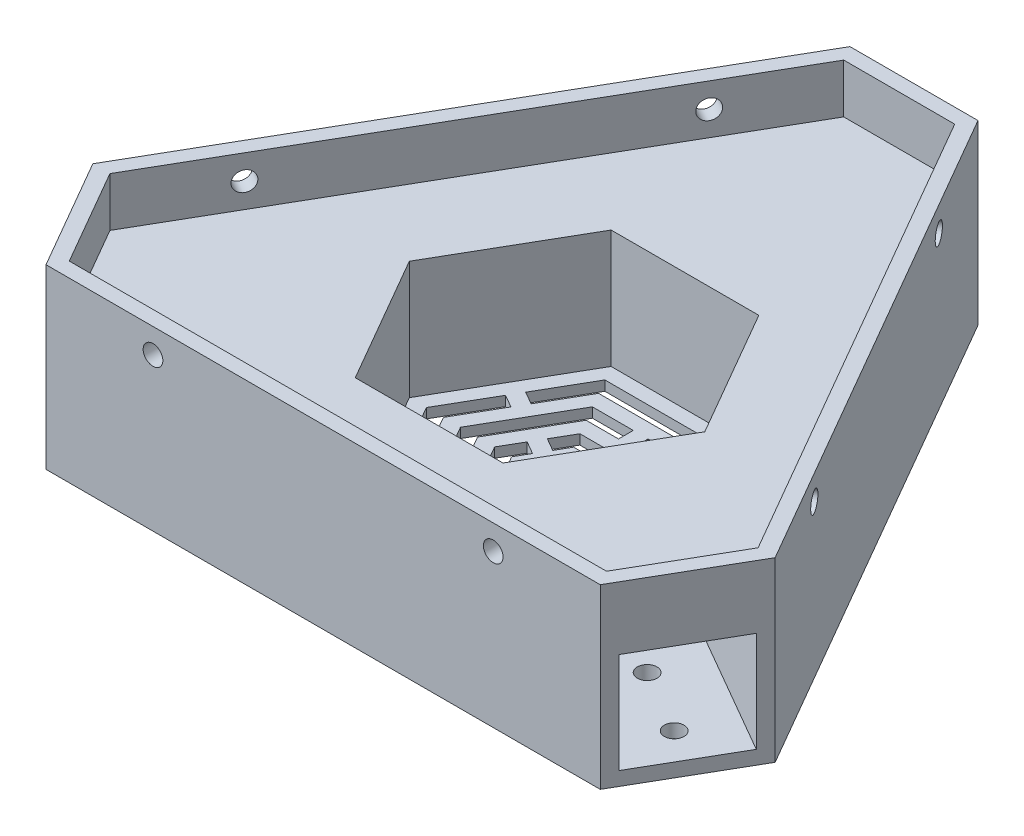
SolidWorks part; units mm, degrees
ref_plane "Front Plane" through (0, 0, 0) normal (0, 0, 1) x (1, 0, 0)
ref_plane "Top Plane" through (0, 0, 0) normal (0, 1, 0) x (1, 0, 0)
ref_plane "Right Plane" through (0, 0, 0) normal (1, 0, 0) x (0, 0, -1)
sketch "Sketch1" plane through (0, 0, 0) normal (0, 1, 0) x (1, 0, 0)
  line L0 (-11.2679, 69.4944) -> (11.2679, 69.4944)
  line L1 (15, 25.9808) -> (-15, 25.9808)
  line L2 (-15, 25.9808) -> (-30, 0)
  line L3 (-30, 0) -> (-15, -25.9808)
  line L4 (-15, -25.9808) -> (15, -25.9808)
  line L5 (15, -25.9808) -> (30, 0)
  line L6 (30, 0) -> (15, 25.9808)
  line L7 (-11.2679, 69.4944) -> (-38.5429, 22.2528)
  line L8 (11.2679, 69.4944) -> (38.5429, 22.2528)
  line L9 (41.141, 23.7528) -> (13, 72.4944)
  line L10 (13, 72.4944) -> (-13, 72.4944)
  line L11 (-13, 72.4944) -> (-41.141, 23.7528)
  line L12 (0, 0) -> (0, 113.4171) construction
  line L13 (0, 0) -> (-77.6761, 44.8463) construction
  line L14 (0, 0) -> (87.0373, 50.251) construction
  line L15 (69.282, -24.9889) -> (41.141, 23.7528)
  line L16 (65.8179, -24.9889) -> (38.5429, 22.2528)
  line L17 (56.282, -47.5056) -> (69.282, -24.9889)
  line L18 (65.8179, -24.9889) -> (54.55, -44.5056)
  line L19 (0, -47.5056) -> (56.282, -47.5056)
  line L20 (54.55, -44.5056) -> (0, -44.5056)
  line L21 (-56.282, -47.5056) -> (0, -47.5056)
  line L22 (-54.55, -44.5056) -> (0, -44.5056)
  line L23 (-69.282, -24.9889) -> (-56.282, -47.5056)
  line L24 (-54.55, -44.5056) -> (-65.8179, -24.9889)
  line L25 (-41.141, 23.7528) -> (-69.282, -24.9889)
  line L26 (-65.8179, -24.9889) -> (-38.5429, 22.2528)
  circle A0 centre (0, 0) radius 25.9808 construction
  point P15 (0, 69.4944)
  point P19 (0, 72.4944)
  point P20 (73.9049, -55.6801)
  point P41 (0, 0)
  dimension "D1" = 30
  dimension "D2" = 3
  dimension "D3" = 3
  dimension "D5" = 26
  dimension "D6" = 120
  dimension "D4" = 3
extrude "Boss-Extrude1" add sketch "Sketch1" along normal blind 2 contours L5 L6 L1 L2 L3 L4 region at (0, 0, 0)
extrude "Boss-Extrude2" add sketch "Sketch1<3>" along normal blind 26 contours L11 L25 L23 L21 L19 L17 L15 L9 L10 L24 L26 L7 L0 L8 L16 L18 L20 L22 | L26 L24 L22 L20 L18 L16 L8 L0 L7 L6 L5 L4 L3 L2 L1 region at (0, 0, -67.7531) region at (53.6241, 0, 1.5346)
sketch "Sketch1<3>" plane through (0, 0, 0) normal (0, 1, 0) x (1, 0, 0) same geometry as "Sketch1"
sketch "Sketch2" plane through (62.782, 0, 36.2472) normal (0.866, 0, 0.5) x (0.5, 0, -0.866)
  line L0 (-13, 26) -> (13, 0) construction
  line L1 (13, 26) -> (-13, 0) construction
  line L3 (-10.2, 2.8) -> (10.2, 2.8)
  line L4 (-10.2, 2.8) -> (-10.2, 23.2)
  line L5 (-10.2, 23.2) -> (10.2, 23.2)
  line L6 (10.2, 2.8) -> (10.2, 23.2)
  line L7 (-10.2, 2.8) -> (10.2, 23.2) construction
  line L8 (-10.2, 23.2) -> (10.2, 2.8) construction
  point P8 (0, 13)
  dimension "D1" = 20.4
extrude "Cut-Extrude1" cut sketch "Sketch2" against normal blind 30
ref_axis "Axis1" through (0, 27.3, 0) along (0, -1, 0)
pattern_circular "CirPattern1" count 3 over 360 about axis through (0, 27.3, 0) along (0, -1, 0) of "Cut-Extrude1"
sketch "Sketch3" plane through (0, 26, 0) normal (0, 1, 0) x (1, 0, 0)
  line L0 (-15, -25.9808) -> (15, -25.9808)
  line L1 (15, -25.9808) -> (30, 0)
  line L2 (30, 0) -> (15, 25.9808)
  line L3 (15, 25.9808) -> (-15, 25.9808)
  line L4 (-15, 25.9808) -> (-30, 0)
  line L5 (-30, 0) -> (-15, -25.9808)
  line L6 (0, -25.9808) -> (0, 25.9808) construction
  line L7 (1.5, 25.9808) -> (1.5, -25.9808) construction
  line L8 (-1.5, 25.9808) -> (-1.5, -25.9808) construction
  line L9 (23.25, -11.6913) -> (-21.75, 14.2894) construction
  line L10 (-22.5, 12.9904) -> (22.5, -12.9904) construction
  line L11 (21.75, -14.2894) -> (-23.25, 11.6913) construction
  line L12 (-21.75, -14.2894) -> (23.25, 11.6913) construction
  line L13 (22.5, 12.9904) -> (-22.5, -12.9904) construction
  line L14 (-23.25, -11.6913) -> (21.75, 14.2894) construction
  line L15 (30, 0) -> (15, 25.9808) construction
  line L16 (0, 22.9808) -> (13.2679, 22.9808)
  line L17 (13.2679, 22.9808) -> (19.1519, 12.7894)
  line L18 (19.1519, 12.7894) -> (16.5538, 11.2894)
  line L19 (16.5538, 11.2894) -> (11.5359, 19.9808)
  line L20 (11.5359, 19.9808) -> (0, 19.9808)
  line L21 (19.6077, 0) -> (9.8038, 16.9808)
  line L22 (9.8038, 16.9808) -> (1.5, 16.9808)
  line L23 (1.5, 16.9808) -> (1.5, 13.9808)
  line L24 (1.5, 13.9808) -> (8.0718, 13.9808)
  line L25 (8.0718, 13.9808) -> (16.1436, 0)
  line L26 (6.1615, 5.2894) -> (8.7596, 6.7894)
  line L27 (8.7596, 6.7894) -> (6.3397, 10.9808)
  line L28 (6.3397, 10.9808) -> (0, 10.9808)
  line L29 (8.7596, 6.7894) -> (10.2596, 4.1913)
  line L30 (6.1615, 5.2894) -> (7.6615, 2.6913)
  line L31 (6.1615, 5.2894) -> (4.6077, 7.9808)
  line L32 (4.6077, 7.9808) -> (1.5, 7.9808)
  line L33 (1.5, 7.9808) -> (0, 7.9808)
  line L34 (1.5, 7.9808) -> (1.5, 4.9808)
  line L35 (1.5, 4.9808) -> (2.8756, 4.9808)
  line L36 (2.8756, 4.9808) -> (5.7513, 0)
  line L37 (7.6615, -2.6913) -> (5.0635, -1.1913)
  line L38 (7.6615, 2.6913) -> (10.2596, 4.1913)
  line L39 (15.4558, -7.1913) -> (12.8577, -5.6913)
  line L40 (20.6519, 10.1913) -> (18.0538, 8.6913)
  line L41 (5.0635, -1.1913) -> (5.7513, 0)
  line L42 (7.6615, 2.6913) -> (9.2154, 0)
  line L43 (7.6615, -2.6913) -> (6.9115, -3.9904)
  line L44 (9.2154, 0) -> (7.6615, -2.6913)
  line L45 (10.2596, 4.1913) -> (12.6795, 0)
  line L46 (12.6795, 0) -> (9.5096, -5.4904)
  line L47 (12.8577, -5.6913) -> (16.1436, 0)
  line L48 (19.6077, 0) -> (15.4558, -7.1913)
  line L49 (18.0538, 8.6913) -> (23.0718, 0)
  line L50 (23.0718, 0) -> (17.3038, -9.9904)
  line L51 (26.5359, 0) -> (20.6519, 10.1913)
  line L52 (19.9019, -11.4904) -> (26.5359, 0)
  line L53 (19.9019, -11.4904) -> (13.2679, -22.9808)
  line L54 (13.2679, -22.9808) -> (1.5, -22.9808)
  line L55 (1.5, -22.9808) -> (1.5, -19.9808)
  line L56 (1.5, -19.9808) -> (11.5359, -19.9808)
  line L57 (11.5359, -19.9808) -> (17.3038, -9.9904)
  line L58 (-9.8038, -16.9808) -> (9.8038, -16.9808)
  line L59 (9.8038, -16.9808) -> (13.9558, -9.7894)
  line L60 (13.9558, -9.7894) -> (11.3577, -8.2894)
  line L61 (11.3577, -8.2894) -> (8.0718, -13.9808)
  line L62 (8.0718, -13.9808) -> (-8.0718, -13.9808)
  line L63 (1.5, -7.9808) -> (1.5, -10.9808)
  line L64 (1.5, -10.9808) -> (6.3397, -10.9808)
  line L65 (6.3397, -10.9808) -> (9.5096, -5.4904)
  line L66 (1.5, -10.9808) -> (-1.5, -10.9808)
  line L67 (1.5, -7.9808) -> (-1.5, -7.9808)
  line L68 (1.5, -7.9808) -> (4.6077, -7.9808)
  line L69 (4.6077, -7.9808) -> (6.1615, -5.2894)
  line L70 (6.1615, -5.2894) -> (6.9115, -3.9904)
  line L71 (6.1615, -5.2894) -> (3.5635, -3.7894)
  line L72 (3.5635, -3.7894) -> (2.8756, -4.9808)
  line L73 (2.8756, -4.9808) -> (-2.8756, -4.9808)
  line L74 (-6.1615, -5.2894) -> (-3.5635, -3.7894)
  line L75 (-1.5, -7.9808) -> (-1.5, -10.9808)
  line L76 (-13.9558, -9.7894) -> (-11.3577, -8.2894)
  line L77 (-1.5, -22.9808) -> (-1.5, -19.9808)
  line L78 (-3.5635, -3.7894) -> (-2.8756, -4.9808)
  line L79 (-1.5, -7.9808) -> (-4.6077, -7.9808)
  line L80 (-6.1615, -5.2894) -> (-6.9115, -3.9904)
  line L81 (-4.6077, -7.9808) -> (-6.1615, -5.2894)
  line L82 (-1.5, -10.9808) -> (-6.3397, -10.9808)
  line L83 (-6.3397, -10.9808) -> (-9.5096, -5.4904)
  line L84 (-11.3577, -8.2894) -> (-8.0718, -13.9808)
  line L85 (-9.8038, -16.9808) -> (-13.9558, -9.7894)
  line L86 (-1.5, -19.9808) -> (-11.5359, -19.9808)
  line L87 (-11.5359, -19.9808) -> (-17.3038, -9.9904)
  line L88 (-13.2679, -22.9808) -> (-1.5, -22.9808)
  line L89 (-19.9019, -11.4904) -> (-13.2679, -22.9808)
  line L90 (-19.9019, -11.4904) -> (-26.5359, 0)
  line L91 (-26.5359, 0) -> (-20.6519, 10.1913)
  line L92 (-20.6519, 10.1913) -> (-18.0538, 8.6913)
  line L93 (-18.0538, 8.6913) -> (-23.0718, 0)
  line L94 (-23.0718, 0) -> (-17.3038, -9.9904)
  line L95 (-9.8038, 16.9808) -> (-19.6077, 0)
  line L96 (-19.6077, 0) -> (-15.4558, -7.1913)
  line L97 (-15.4558, -7.1913) -> (-12.8577, -5.6913)
  line L98 (-12.8577, -5.6913) -> (-16.1436, 0)
  line L99 (-16.1436, 0) -> (-8.0718, 13.9808)
  line L100 (-7.6615, 2.6913) -> (-10.2596, 4.1913)
  line L101 (-10.2596, 4.1913) -> (-12.6795, 0)
  line L102 (-12.6795, 0) -> (-9.5096, -5.4904)
  line L103 (-10.2596, 4.1913) -> (-8.7596, 6.7894)
  line L104 (-7.6615, 2.6913) -> (-6.1615, 5.2894)
  line L105 (-7.6615, 2.6913) -> (-9.2154, 0)
  line L106 (-9.2154, 0) -> (-7.6615, -2.6913)
  line L107 (-7.6615, -2.6913) -> (-6.9115, -3.9904)
  line L108 (-7.6615, -2.6913) -> (-5.0635, -1.1913)
  line L109 (-5.0635, -1.1913) -> (-5.7513, 0)
  line L110 (-5.7513, 0) -> (-2.8756, 4.9808)
  line L111 (-1.5, 7.9808) -> (-1.5, 4.9808)
  line L112 (-6.1615, 5.2894) -> (-8.7596, 6.7894)
  line L113 (-1.5, 16.9808) -> (-1.5, 13.9808)
  line L114 (-19.1519, 12.7894) -> (-16.5538, 11.2894)
  line L115 (-1.5, 4.9808) -> (-2.8756, 4.9808)
  line L116 (-6.1615, 5.2894) -> (-4.6077, 7.9808)
  line L117 (-1.5, 7.9808) -> (0, 7.9808)
  line L118 (-4.6077, 7.9808) -> (-1.5, 7.9808)
  line L119 (-8.7596, 6.7894) -> (-6.3397, 10.9808)
  line L120 (-6.3397, 10.9808) -> (0, 10.9808)
  line L121 (-1.5, 13.9808) -> (-8.0718, 13.9808)
  line L122 (-9.8038, 16.9808) -> (-1.5, 16.9808)
  line L123 (-16.5538, 11.2894) -> (-11.5359, 19.9808)
  line L124 (-11.5359, 19.9808) -> (0, 19.9808)
  line L125 (-13.2679, 22.9808) -> (-19.1519, 12.7894)
  line L126 (0, 22.9808) -> (-13.2679, 22.9808)
  line L127 (-1.5, 4.9808) -> (1.5, 4.9808)
  line L128 (5.0635, -1.1913) -> (3.5635, -3.7894)
  line L129 (-5.0635, -1.1913) -> (-3.5635, -3.7894)
  line L130 (15, 25.9808) -> (0, 0) construction
  point P34 (0, 0)
  point P58 (6.9115, 3.9904)
  point P66 (4.3135, 2.4904)
  point P68 (9.5096, 5.4904)
  point P71 (12.1077, 6.9904)
  point P72 (14.7058, 8.4904)
  point P76 (13.2679, 22.9808)
  point P78 (12.8577, 20.2978)
  point P79 (13.2679, 16.9808)
  point P80 (8.1205, 14.065)
  point P86 (6.4287, 9.0261)
  point P96 (0, 0)
  point P101 (3.2877, 5.6945)
  point P104 (0, -7.9808)
  point P112 (0, -4.9808)
  point P114 (0, -10.9808)
  point P117 (0, -13.9808)
  point P118 (0, -16.9808)
  point P123 (4.9027, 9.0261)
  point P129 (0, 0)
  point P139 (0, 9.0261)
  point P147 (-6.9115, 3.9904)
  point P155 (-4.3135, 2.4904)
  point P156 (5.2112, 9.0261)
  point P157 (-9.5096, 5.4904)
  point P158 (4.9027, 9.0261)
  point P160 (-12.1077, 6.9904)
  point P161 (-14.7058, 8.4904)
  point P162 (-4.9027, 9.0261)
  point P164 (1.5, 7.9808)
  point P165 (0, 0)
  point P166 (3.2684, 5.6611)
  point P167 (0, 0)
  point P168 (0, 0)
  point P169 (0, 0)
  point P170 (6.1615, 10.4199)
  point P171 (6.9115, 11.9028)
  point P172 (3.6742, 6.3639)
  point P173 (-1.5, 6.3639)
  point P174 (3.6742, -6.3639)
  point P175 (3.6742, 6.3639)
  point P176 (0, 0)
  point P177 (1.5, 6.103)
  point P178 (2.8756, 4.9808)
  dimension "D1" = 3
  dimension "D4" = 3
  dimension "D5" = 6
  dimension "D6" = 9
  dimension "D7" = 12
  dimension "D8" = 15
  dimension "D9" = 18
  dimension "D10" = 3
  dimension "D2" = 3
  dimension "D3" = 3
extrude "Cut-Extrude2" cut sketch "Sketch3" against normal through all contours L109 L129 L78 L73 L72 L128 L41 L36 L35 L127 L115 L110 | L70 L69 L68 L63 L64 L65 L46 L45 L38 L42 L44 L43 | L120 L119 L112 L116 L118 L117 L33 L32 L31 L26 L27 L28 | L107 L106 L105 L100 L101 L102 L83 L82 L75 L79 L81 L80 | L85 L58 L59 L60 L61 L62 L84 L76 | L48 L21 L22 L23 L24 L25 L47 L39 | L122 L95 L96 L97 L98 L99 L121 L113 | L16 L126 L125 L114 L123 L124 L20 L19 L18 L17 | L94 L93 L92 L91 L90 L89 L88 L77 L86 L87 | L57 L56 L55 L54 L53 L52 L51 L40 L49 L50 region at (6.634, 26, -22.5803) region at (12.18, 26, -7.0321) region at (0, 26, -8.8372) region at (7.6533, 26, 4.4186) region at (0, 26, 0) region at (-7.6533, 26, 4.4186) region at (23.234, 26, -4.8879) region at (0, 26, 14.0642) region at (-7.384, 26, 22.5652) region at (-12.18, 26, -7.0321)
sketch "Sketch4" plane through (0, 0, 0) normal (0, -1, 0) x (1, 0, 0)
  line L0 (0, -72.4944) -> (0, 0) construction
  line L1 (13, -72.4944) -> (-13, -72.4944) construction
  line L2 (-62.782, 36.2472) -> (0, 0) construction
  line L3 (62.782, 36.2472) -> (0, 0) construction
  circle A0 centre (0, -64.9944) radius 2
  circle A1 centre (0, -49.9944) radius 2
  circle A2 centre (-56.2868, 32.4972) radius 2
  circle A3 centre (-43.2965, 24.9972) radius 2
  circle A4 centre (56.2868, 32.4972) radius 2
  circle A5 centre (43.2965, 24.9972) radius 2
  point P21 (0, 0)
  dimension "D3" = 4
  dimension "D1" = 7.5
  dimension "D2" = 15
  dimension "D4" = 3
extrude "Cut-Extrude3" cut sketch "Sketch4" against normal blind 10
extrude "Boss-Extrude4" add sketch "Sketch1<5>" along normal blind 10 from surface contours L11 L25 L23 L21 L19 L17 L15 L9 L10 L24 L26 L7 L0 L8 L16 L18 L20 L22 region at (53.6241, 0, 1.5346) starting at face at (0, 26, 0)
sketch "Sketch1<5>" plane through (0, 0, 0) normal (0, 1, 0) x (1, 0, 0) same geometry as "Sketch1"
sketch "Sketch5" plane through (-38.5429, 0, -22.2528) normal (0.866, 0, 0.5) x (0.5, 0, -0.866)
  line L0 (-54.55, 31) -> (54.55, 31) construction
  line L1 (-54.55, 36) -> (-54.55, 26) construction
  line L2 (54.55, 36) -> (54.55, 26) construction
  line L3 (0, 36) -> (0, 26) construction
  line L4 (54.55, 36) -> (-54.55, 36) construction
  line L5 (54.55, 26) -> (-54.55, 26) construction
  circle A0 centre (-34.55, 31) radius 2
  circle A1 centre (34.55, 31) radius 2
  dimension "D2" = 4
  dimension "D1" = 20
extrude "Cut-Extrude4" cut sketch "Sketch5" against normal blind 10
pattern_circular "CirPattern2" count 3 over 360 about axis through (0, 27.3, 0) along (0, -1, 0) of "Cut-Extrude4"
